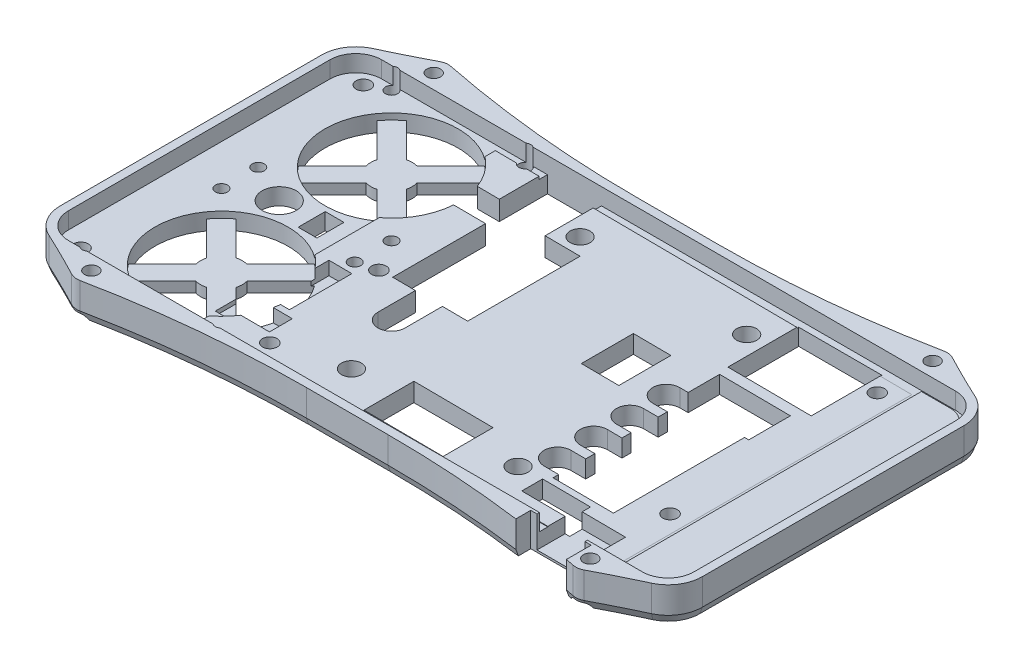
SolidWorks part; units mm, degrees
ref_plane "前视基准面" through (0, 0, 0) normal (0, 0, 1) x (1, 0, 0)
ref_plane "上视基准面" through (0, 0, 0) normal (0, 1, 0) x (1, 0, 0)
ref_plane "右视基准面" through (0, 0, 0) normal (1, 0, 0) x (0, 0, -1)
sketch "草图1" plane through (0, 0, 0) normal (0, 1, 0) x (1, 0, 0)
  line L0 (6, 0.2) -> (143.8, 0.2)
  line L1 (6, 0) -> (143.8, 0) construction
  line L2 (0, -6) -> (0, -68.8) construction
  line L3 (6, -74.8) -> (143.8, -74.8) construction
  line L4 (149.8, -6) -> (149.8, -68.8) construction
  line L5 (150, -6) -> (150, -68.8)
  line L6 (6, -75) -> (143.8, -75)
  line L7 (-0.2, -6) -> (-0.2, -68.8)
  arc A0 (143.8, 0) -> (149.8, -6) centre (143.8, -6) cw construction
  arc A1 (143.8, -74.8) -> (149.8, -68.8) centre (143.8, -68.8) ccw construction
  arc A2 (0, -68.8) -> (6, -74.8) centre (6, -68.8) ccw construction
  arc A3 (6, 0) -> (0, -6) centre (6, -6) ccw construction
  arc A4 (143.8, 0.2) -> (150, -6) centre (143.8, -6) cw
  arc A5 (143.8, -75) -> (150, -68.8) centre (143.8, -68.8) ccw
  arc A6 (-0.2, -68.8) -> (6, -75) centre (6, -68.8) ccw
  arc A7 (6, 0.2) -> (-0.2, -6) centre (6, -6) ccw
  point P7 (149.8, 0)
  point P12 (0, -74.8)
  point P15 (0, 0)
  dimension "D3" = 6
  dimension "D1" = 74.8
  dimension "D2" = 149.8
  dimension "D4" = 0.2
extrude "凸台-拉伸1" add sketch "草图1" along normal blind 4
sketch "草图2" plane through (0, 0, 0) normal (0, -1, 0) x (-1, 0, 0)
  line L0 (-122.6, -55.35) -> (-108.9, -55.35)
  line L1 (-122.6, -69.85) -> (-108.9, -69.85)
  line L2 (-122.6, -69.85) -> (-122.6, -63.95)
  line L3 (-122.6, -63.95) -> (-108.9, -63.95)
  line L4 (-108.9, -69.85) -> (-108.9, -63.95)
  line L5 (-135.3, -1.25) -> (-35.3, -1.25) construction
  line L6 (-135.3, -1.25) -> (-135.3, -73.55) construction
  line L7 (-135.3, -73.55) -> (-35.3, -73.55) construction
  line L8 (-35.3, -1.25) -> (-35.3, -73.55) construction
  line L9 (-108.9, -61.25) -> (-108.9, -55.35)
  line L10 (-122.6, -61.25) -> (-108.9, -61.25)
  line L11 (-122.6, -61.25) -> (-122.6, -55.35)
  line L12 (-122.6, -46.75) -> (-108.9, -46.75)
  line L13 (-108.9, -52.65) -> (-108.9, -46.75)
  line L14 (-122.6, -52.65) -> (-108.9, -52.65)
  line L15 (-122.6, -52.65) -> (-122.6, -46.75)
  line L16 (-122.6, -38.15) -> (-108.9, -38.15)
  line L17 (-108.9, -44.05) -> (-108.9, -38.15)
  line L18 (-122.6, -44.05) -> (-108.9, -44.05)
  line L19 (-122.6, -44.05) -> (-122.6, -38.15)
  line L20 (0, -6) -> (0, -68.8) construction
  line L21 (-35.3, -73.55) -> (-0.8, -73.55) construction
  line L22 (-120.25, -26.65) -> (-111.25, -26.65) construction
  line L23 (-120.25, -26.65) -> (-120.25, -33.15) construction
  line L24 (-120.25, -33.15) -> (-111.25, -33.15) construction
  line L25 (-111.25, -26.65) -> (-111.25, -33.15) construction
  line L26 (-85.8, -48.75) -> (-81.1, -48.75) construction
  line L27 (-85.8, -48.75) -> (-85.8, -58.15) construction
  line L28 (-85.8, -58.15) -> (-81.1, -58.15) construction
  line L29 (-81.1, -48.75) -> (-81.1, -58.15) construction
  line L30 (-71.5, -48.65) -> (-68.2, -48.65) construction
  line L31 (-71.5, -48.65) -> (-71.5, -57.55) construction
  line L32 (-71.5, -57.55) -> (-68.2, -57.55) construction
  line L33 (-68.2, -48.65) -> (-68.2, -57.55) construction
  line L34 (-43.1, -45.05) -> (-38.6, -45.05) construction
  line L35 (-43.1, -45.05) -> (-43.1, -59.05) construction
  line L36 (-43.1, -59.05) -> (-38.6, -59.05) construction
  line L37 (-38.6, -45.05) -> (-38.6, -59.05) construction
  line L38 (-45.3, -61.55) -> (-33.3, -61.55) construction
  line L39 (-45.3, -61.55) -> (-45.3, -66.05) construction
  line L40 (-45.3, -66.05) -> (-33.3, -66.05) construction
  line L41 (-33.3, -61.55) -> (-33.3, -66.05) construction
  line L42 (-0.8, -73.55) -> (-0.8, -1.25) construction
  line L43 (-0.8, -1.25) -> (-35.3, -1.25) construction
  line L44 (-149.8, -6) -> (-149.8, -68.8) construction
  line L45 (-30.8, -34.65) -> (-27.3, -34.65) construction
  line L46 (-30.8, -34.65) -> (-30.8, -40.15) construction
  line L47 (-30.8, -40.15) -> (-27.3, -40.15) construction
  line L48 (-27.3, -34.65) -> (-27.3, -40.15) construction
  line L49 (-120.75, -33.65) -> (-110.75, -33.65)
  line L50 (-110.75, -26.15) -> (-110.75, -33.65)
  line L51 (-120.75, -26.15) -> (-110.75, -26.15)
  line L52 (-120.75, -26.15) -> (-120.75, -33.65)
  line L53 (-86.3, -48.25) -> (-86.3, -58.65)
  line L54 (-86.3, -58.65) -> (-80.6, -58.65)
  line L55 (-80.6, -48.25) -> (-80.6, -58.65)
  line L56 (-86.3, -48.25) -> (-80.6, -48.25)
  line L57 (-72, -48.15) -> (-72, -58.05)
  line L58 (-72, -58.05) -> (-67.7, -58.05)
  line L59 (-67.7, -48.15) -> (-67.7, -58.05)
  line L60 (-72, -48.15) -> (-67.7, -48.15)
  line L61 (-31.3, -34.15) -> (-31.3, -40.65)
  line L62 (-31.3, -40.65) -> (-26.8, -40.65)
  line L63 (-26.8, -34.15) -> (-26.8, -40.65)
  line L64 (-31.3, -34.15) -> (-26.8, -34.15)
  line L65 (-43.6, -44.55) -> (-43.6, -59.55)
  line L66 (-43.6, -59.55) -> (-38.1, -59.55)
  line L67 (-38.1, -44.55) -> (-38.1, -59.55)
  line L68 (-43.6, -44.55) -> (-38.1, -44.55)
  line L69 (-45.8, -61.05) -> (-45.8, -66.55)
  line L70 (-45.8, -66.55) -> (-32.8, -66.55)
  line L71 (-32.8, -61.05) -> (-32.8, -66.55)
  line L72 (-45.8, -61.05) -> (-32.8, -61.05)
  circle A0 centre (-103.2, -9.35) radius 2 construction
  circle A1 centre (-103.2, -64.25) radius 2 construction
  circle A2 centre (-63.2, -64.25) radius 2 construction
  circle A3 centre (-63.2, -9.35) radius 2 construction
  circle A4 centre (-130.8, -5.6) radius 1.25 construction
  circle A5 centre (-131.1, -55.65) radius 1.25 construction
  circle A6 centre (-47.7, -4.85) radius 1.25 construction
  circle A7 centre (-48.1, -68.75) radius 1.25 construction
  circle A8 centre (-22.8, -70.3) radius 1.25 construction
  circle A9 centre (-5.05, -71.05) radius 1.25 construction
  circle A10 centre (-5.05, -3.25) radius 1.25 construction
  circle A11 centre (-19, -37.4) radius 3.6 construction
  circle A12 centre (-103.2, -9.35) radius 2.4
  circle A13 centre (-63.2, -9.35) radius 2.4
  circle A14 centre (-63.2, -64.25) radius 2.4
  circle A15 centre (-103.2, -64.25) radius 2.4
  circle A16 centre (-19, -37.4) radius 4.1
  circle A17 centre (-130.8, -5.6) radius 1.75
  circle A18 centre (-131.1, -55.65) radius 1.75
  circle A19 centre (-48.1, -68.75) radius 1.75
  circle A20 centre (-22.8, -70.3) radius 1.75
  circle A21 centre (-5.05, -71.05) radius 1.75
  circle A22 centre (-5.05, -3.25) radius 1.75
  circle A23 centre (-47.7, -4.85) radius 1.75
  circle A24 centre (-46.11, -40.57) radius 1.25 construction
  circle A25 centre (-46.11, -40.57) radius 1.75
  point P22 (0, -37.4)
  point P23 (-135.3, -37.4)
  point P28 (-115.75, -33.15)
  point P29 (-115.75, -38.15)
  point P30 (-111.25, -29.9)
  point P31 (-108.9, -41.1)
  point P79 (-0.8, -37.4)
  point P81 (-27.3, -37.4)
  dimension "D21" = 4
  dimension "D34" = 2.5
  dimension "D53" = 7.2
  dimension "D1" = 13.7
  dimension "D2" = 5.9
  dimension "D3" = 72.3
  dimension "D4" = 3.7
  dimension "D5" = 12.7
  dimension "D7" = 14.5
  dimension "D8" = 100
  dimension "D9" = 2.7
  dimension "D10" = 9
  dimension "D11" = 6.5
  dimension "D12" = 11.2
  dimension "D13" = 15.4
  dimension "D14" = 9.4
  dimension "D15" = 4.7
  dimension "D16" = 23.1
  dimension "D17" = 3.3
  dimension "D18" = 8.9
  dimension "D19" = 16
  dimension "D20" = 37.4
  dimension "D22" = 8.1
  dimension "D23" = 32.1
  dimension "D24" = 40
  dimension "D25" = 9.3
  dimension "D26" = 14
  dimension "D27" = 4.5
  dimension "D28" = 12
  dimension "D29" = 4.5
  dimension "D30" = 3.3
  dimension "D31" = 2
  dimension "D32" = 7.5
  dimension "D33" = 14.5
  dimension "D35" = 34.5
  dimension "D36" = 2
  dimension "D37" = 4.25
  dimension "D38" = 2.5
  dimension "D39" = 3.25
  dimension "D40" = 22
  dimension "D41" = 4.8
  dimension "D42" = 12.8
  dimension "D43" = 3.6
  dimension "D44" = 12.4
  dimension "D45" = 4.35
  dimension "D46" = 4.5
  dimension "D47" = 4.2
  dimension "D48" = 17.9
  dimension "D49" = 18.2
  dimension "D50" = 3.5
  dimension "D51" = 5.5
  dimension "D52" = 8.3
  dimension "D58" = 28.18
  dimension "D59" = 1.99
  dimension "D54" = 0.4
  dimension "D55" = 0.5
  dimension "D56" = 0.5
  dimension "D57" = 0.5
  dimension "D6" = 4
sketch "草图7" plane through (0, 0, -0.2) normal (0, 0, -1) x (-1, 0, 0)
  line L0 (-135.3, 4) -> (-35.3, 4.75)
  line L2 (-35.3, 4.75) -> (-35.3, 4)
  line L4 (-35.3, 4) -> (-135.3, 4)
  line L6 (-143.8, 4) -> (-6, 4) construction
  dimension "D1" = 0.75
extrude "凸台-拉伸11" add sketch "草图7" against normal offset from surface (71.2 mm away) 2 from offset 2 up to face at (74.9, 2, 75) offset against normal yes
extrude "切除-拉伸1" cut sketch "草图2" against normal blind 10 contours A12 | A13 | A14 | A15
sketch "草图3" plane through (0, 0, 0) normal (0, 1, 0) x (1, 0, 0)
  line L0 (136.8, -1) -> (136.8, -73.8)
  line L1 (143.8, 0) -> (135.8, 0) construction
  line L2 (149.8, -6) -> (149.8, -68.8) construction
  line L3 (143.8, -74.8) -> (135.8, -74.8) construction
  line L4 (135.8, 0) -> (135.8, -74.8) construction
  line L5 (6, -74.8) -> (143.8, -74.8) construction
  line L6 (135.3, -1.25) -> (135.3, -73.55) construction
  line L7 (143.8, -73.8) -> (136.8, -73.8)
  line L8 (148.8, -6) -> (148.8, -68.8)
  line L9 (143.8, -1) -> (136.8, -1)
  arc A0 (143.8, 0) -> (149.8, -6) centre (143.8, -6) cw construction
  arc A1 (149.8, -68.8) -> (143.8, -74.8) centre (143.8, -68.8) cw construction
  arc A2 (148.8, -68.8) -> (143.8, -73.8) centre (143.8, -68.8) cw
  arc A3 (143.8, -1) -> (148.8, -6) centre (143.8, -6) cw
  point P17 (149.8, 0)
  dimension "D1" = 6
  dimension "D2" = 0.5
extrude "凸台-拉伸9" add sketch "草图3" along normal offset from surface (5 mm away) 1 up to face at (85.3, 4, 37.4) offset beyond the face yes
sketch "草图4" plane through (0, 0, 0) normal (0, 1, 0) x (1, 0, 0)
  line L0 (125.2, -20.85) -> (108.2, -20.85)
  line L1 (108.2, -30.85) -> (109.7, -30.85)
  line L2 (109.7, -30.85) -> (109.7, -62.35)
  line L3 (108.7, -68.85) -> (108.7, -62.35)
  line L4 (49.2, -40.35) -> (49.2, -13.35)
  line L5 (108.2, -30.85) -> (108.2, -20.85)
  line L6 (108.7, -68.85) -> (120.2, -68.85)
  line L7 (108.2, -30.85) -> (125.2, -30.85) construction
  line L8 (109.7, -62.35) -> (124.2, -62.35)
  line L9 (80.466, -18.85) -> (96.6871, -18.85) construction
  line L10 (107.2, 11.628) -> (107.2, 24.7853) construction
  line L11 (49.2, -13.35) -> (67.2, -13.35)
  line L12 (125.2, -30.85) -> (124.2, -30.85)
  line L13 (124.2, -30.85) -> (124.2, -62.35)
  line L14 (124.2, -62.35) -> (120.2, -62.35)
  line L15 (120.2, -62.35) -> (120.2, -68.85)
  line L16 (67.2, -13.35) -> (67.2, -40.35)
  line L17 (67.2, -40.35) -> (49.2, -40.35)
  line L18 (63.2, -9.35) -> (46.0308, -9.35) construction
  line L19 (106.2, -55.55) -> (106.2, -28.85) construction
  line L20 (108.7, -63.85) -> (120.2, -63.85)
  line L21 (125.2, -20.85) -> (125.2, -30.85)
  line L22 (106.2, -28.4) -> (108.2, -28.4)
  line L23 (106.2, -34.9) -> (109.7, -34.9)
  line L24 (106.2, -37.1) -> (109.7, -37.1)
  line L25 (109.7, -37.1) -> (109.7, -43.6)
  line L26 (109.7, -43.6) -> (106.2, -43.6)
  line L27 (106.2, -45.8) -> (109.7, -45.8)
  line L28 (106.2, -52.3) -> (109.7, -52.3)
  line L29 (106.2, -54.5) -> (109.7, -54.5)
  line L30 (106.2, -61) -> (109.7, -61)
  line L31 (54.65, -49.35) -> (54.65, -40.35)
  line L32 (61.15, -49.35) -> (61.15, -40.35)
  line L33 (89.5, -35.35) -> (89.5, -22.85)
  line L34 (89.5, -22.85) -> (98.5, -22.85)
  line L35 (98.5, -22.85) -> (98.5, -35.35)
  line L36 (98.5, -35.35) -> (89.5, -35.35)
  line L37 (58.8, -1.85) -> (58.8, -13.85)
  line L38 (58.8, -13.85) -> (45.8, -13.85)
  line L39 (107.7, -18.35) -> (107.7, -1.35)
  line L40 (107.7, -1.35) -> (127.7, -1.35)
  line L41 (127.7, -1.35) -> (127.7, -18.35)
  line L42 (127.7, -18.35) -> (107.7, -18.35)
  line L43 (92.2, -59.25) -> (92.2, -71.25)
  line L44 (92.2, -71.25) -> (73.2, -71.25)
  line L45 (73.2, -71.25) -> (73.2, -59.25)
  line L46 (73.2, -59.25) -> (92.2, -59.25)
  line L47 (45.8, -13.85) -> (45.8, -1.85)
  line L48 (45.8, -1.85) -> (58.8, -1.85)
  line L49 (45.8, -11.35) -> (39.8, -11.35)
  line L50 (39.8, -11.35) -> (39.8, -18.05)
  line L51 (39.8, -18.05) -> (45.8, -18.05)
  line L52 (45.8, -18.05) -> (45.8, -11.35)
  line L53 (45.8, -18.05) -> (49.2, -18.05)
  line L54 (45.8, -1.85) -> (45.8, 0.2)
  line L55 (143.8, 0.2) -> (6, 0.2) construction
  line L56 (45.8, 0.2) -> (58.8, 0.2)
  line L57 (58.8, 0.2) -> (58.8, -1.85)
  circle A0 centre (103.2, -9.35) radius 2.4 construction
  circle A1 centre (103.2, -64.25) radius 2.4 construction
  circle A2 centre (103.2, -64.25) radius 2.4
  circle A3 centre (63.2, -64.25) radius 2.4 construction
  circle A4 centre (63.2, -64.25) radius 2.4
  circle A5 centre (103.2, -9.35) radius 2.4 construction
  circle A6 centre (106.2, -31.65) radius 3.25
  circle A7 centre (106.2, -40.35) radius 3.25
  circle A8 centre (106.2, -49.05) radius 3.25
  circle A9 centre (106.2, -57.75) radius 3.25
  circle A10 centre (63.2, -9.35) radius 2.4 construction
  circle A11 centre (63.2, -9.35) radius 2.4 construction
  circle A12 centre (57.9, -49.35) radius 3.25
  point P30 (67.2, -26.85)
  dimension "D7" = 9.5
  dimension "D30" = 4.5
  dimension "D40" = 6.5
  dimension "D18" = 6.5
  dimension "D21" = 4.5
  dimension "D4" = 11.5
  dimension "D5" = 48
  dimension "D6" = 10
  dimension "D8" = 4
  dimension "D9" = 5
  dimension "D10" = 5
  dimension "D11" = 17
  dimension "D12" = 6.5
  dimension "D13" = 1
  dimension "D14" = 14
  dimension "D15" = 18
  dimension "D16" = 4
  dimension "D17" = 27
  dimension "D19" = 40
  dimension "D20" = 5.3
  dimension "D22" = 4.4
  dimension "D23" = 13
  dimension "D24" = 1.5
  dimension "D25" = 12.5
  dimension "D26" = 5.5
  dimension "D27" = 9
  dimension "D28" = 8.7
  dimension "D29" = 12
  dimension "D31" = 20
  dimension "D32" = 9
  dimension "D33" = 17
  dimension "D34" = 11
  dimension "D35" = 19
  dimension "D36" = 12
  dimension "D37" = 7
  dimension "D38" = 11.5
  dimension "D39" = 22.3
  dimension "D41" = 3
  dimension "D43" = 13.5
  dimension "D44" = 4.7
  dimension "D45" = 6
  dimension "D46" = 2.5
  dimension "D47" = 6.7
  dimension "D42" = 4
extrude "拉伸-薄壁1" add sketch "草图1<2>" along normal blind 8 thin thin type one direction wall 2
sketch "草图1<2>" plane through (0, 0, 0) normal (0, 1, 0) x (1, 0, 0) same geometry as "草图1"
extrude "切除-拉伸2" cut sketch "草图4" along normal through all contours L20 L3 L6 L15 | A9 L30 L2 L29 | A8 L28 L2 L27 | A7 L26 L2 L24 | A6 L23 L2 L1 | A6 L5 L22 | A12 L17 L31 | A12 L32 L17 | L52 L53 L4 L38 | L57 L56 L54 L48 | L41 L42 L39 L40 | L8 L2 L1 L5 L0 L21 L12 L13 | A6 | A7 | A8 | A9 | L46 L43 L44 L45 | L35 L36 L33 L34 | L4 L11 L16 L17 | A12 | L47 L48 L37 L38 | L50 L51 L52 L49 region at (114.45, 0, 66.35) region at (107.7112, 0, 28.6021) region at (108.9903, 0, 33.7511) region at (109.6262, 0, 40.35) region at (107.95, 0, 60.9262) region at (109.6262, 0, 49.05) region at (47.5, 0, 15.95) region at (57.9, 0, 43.6145) region at (52.3, 0, 0.825)
extrude "切除-拉伸3" cut sketch "草图2<11>" against normal through all contours L61 L62 L63 L64 | A16
sketch "草图2<11>" plane through (0, 0, 0) normal (0, -1, 0) x (-1, 0, 0) same geometry as "草图2"
extrude "切除-拉伸4" cut sketch "草图2<13>" against normal through all contours A17 | A18 | A19 | A23 | A22 | A21 | A25
sketch "草图2<13>" plane through (0, 0, 0) normal (0, -1, 0) x (-1, 0, 0) same geometry as "草图2"
extrude "切除-拉伸5" cut sketch "草图2<14>" against normal through all from offset 1.5 contours L67 L66 L65 L68 | L71 L70 L69 L72 offset against normal yes
sketch "草图2<14>" plane through (0, 0, 0) normal (0, -1, 0) x (-1, 0, 0) same geometry as "草图2"
sketch "草图5" plane through (0, 0, 0) normal (0, -1, 0) x (-1, 0, 0)
  text T0 "<b>M3*6</b>" font "@Adobe 黑体 Std R" height 7
  text T1 "<b>M3*6</b>" font "@Adobe 黑体 Std R" height 7
  text T2 "<b>M3*6</b>" font "@Adobe 黑体 Std R" height 7
  text T3 "<b>M3*6</b>" font "@Adobe 黑体 Std R" height 7
extrude "切除-拉伸6" [suppressed] cut sketch "草图5" against normal blind 0.6
sketch "草图6" plane through (0, 0, 0) normal (0, 1, 0) x (1, 0, 0)
  line L1 (0, -6) -> (0, -68.8) construction
  line L2 (149.8, -6) -> (149.8, -68.8) construction
  line L4 (6, 0.2) -> (143.8, 0.2) construction
  line L5 (6, -75) -> (143.8, -75) construction
  circle A0 centre (15, 3.7) radius 1.5 construction
  circle A1 centre (15, -78.5) radius 1.5 construction
  circle A2 centre (134.8, 3.7) radius 1.5 construction
  circle A3 centre (134.8, -78.5) radius 1.5 construction
  circle A4 centre (15, 3.7) radius 3.5
  circle A5 centre (15, -78.5) radius 3.5
  circle A6 centre (134.8, 3.7) radius 3.5
  circle A7 centre (134.8, -78.5) radius 3.5
  circle A8 centre (15, 3.7) radius 1.65
  circle A9 centre (134.8, 3.7) radius 1.65
  circle A10 centre (134.8, -78.5) radius 1.65
  circle A11 centre (15, -78.5) radius 1.65
  dimension "D1" = 3
  dimension "D3" = 0.15
  dimension "D4" = 15
  dimension "D5" = 15
  dimension "D2" = 2
extrude "凸台-拉伸10" add sketch "草图6" along normal up to surface (8 mm away) up to face at (74.9, 8, 37.4)
extrude "切除-拉伸9" cut sketch "草图6<2>" along normal through all contours A8 | A9 | A10 | A11
sketch "草图6<2>" plane through (0, 0, 0) normal (0, 1, 0) x (1, 0, 0) same geometry as "草图6"
fillet "圆角1" radius 250 8 edges at (18.1623, 4, 77) (11.8377, 4, 77) (131.6377, 4, 77) (137.9623, 4, 77) (137.9623, 4, -2.2) (131.6377, 4, -2.2) (11.8377, 4, -2.2) (18.1623, 4, -2.2)
chamfer "倒角1" distance 0.6 angle 70 20 edges at (40.2731, 0, 78.2358) (14.5029, 0, 81.9645) (74.9, 0, 77) (7.988, 0, 78.8506) (109.5269, 0, 78.2358) (-0.9143, 0, 73.2083) (135.2971, 0, 81.9645) (-2.2, 0, 37.4) (141.812, 0, 78.8506) (-0.9143, 0, 1.5917) (150.7143, 0, 73.2083) (7.988, 0, -4.0506) (152, 0, 37.4) (14.5029, 0, -7.1645) (150.7143, 0, 1.5917) (40.2731, 0, -3.4358) (141.812, 0, -4.0506) (74.9, 0, -2.2) (135.2971, 0, -7.1645) (109.5269, 0, -3.4358) first distance on face at (134.8, 0, 80.15)
sketch "草图8" plane through (0, 0, 0) normal (0, -1, 0) x (1, 0, 0)
  line L0 (9.5525, 32.9807) -> (9.5525, 0.9807) construction
  line L1 (9.5525, 0.9807) -> (41.5525, 0.9807) construction
  line L2 (41.5525, 0.9807) -> (41.5525, 32.9807) construction
  line L3 (41.5525, 32.9807) -> (9.5525, 32.9807) construction
  line L4 (31.3, 37.4) -> (26.8, 37.4) construction
  line L7 (41.5525, 41.8193) -> (9.5525, 41.8193) construction
  line L8 (41.5525, 73.8193) -> (41.5525, 41.8193) construction
  line L9 (9.5525, 73.8193) -> (41.5525, 73.8193) construction
  line L10 (9.5525, 41.8193) -> (9.5525, 73.8193) construction
  circle A0 centre (41.5525, 0.9807) radius 1.45
  circle A1 centre (41.5525, 32.9807) radius 1.45
  circle A2 centre (9.5525, 32.9807) radius 1.45
  circle A3 centre (9.5525, 0.9807) radius 1.45
  circle A4 centre (9.5525, 73.8193) radius 1.45
  circle A5 centre (9.5525, 41.8193) radius 1.45
  circle A6 centre (41.5525, 41.8193) radius 1.45
  circle A7 centre (41.5525, 73.8193) radius 1.45
  point P4 (9.5525, 16.9807)
  dimension "D3" = 2.9
  dimension "D4" = 2.9
  dimension "D5" = 2.9
  dimension "D6" = 2.9
  dimension "D1" = 32
  dimension "D2" = 32
extrude "切除-拉伸10" cut sketch "草图8" against normal through all
sketch "草图9" plane through (0, 0, 0) normal (0, -1, 0) x (1, 0, 0)
  line L0 (9.5525, 32.9807) -> (41.5525, 32.9807) construction
  line L1 (41.5525, 32.9807) -> (41.5525, 0.9807) construction
  line L2 (41.5525, 0.9807) -> (9.5525, 0.9807) construction
  line L3 (9.5525, 0.9807) -> (9.5525, 32.9807) construction
  line L4 (9.5525, 32.9807) -> (41.5525, 0.9807) construction
  line L5 (41.5525, 32.9807) -> (9.5525, 0.9807) construction
  line L6 (13.088, 32.9807) -> (41.5525, 4.5163)
  line L7 (41.5525, 4.5163) -> (38.017, 0.9807)
  line L8 (38.017, 0.9807) -> (9.5525, 29.4452)
  line L9 (9.5525, 29.4452) -> (13.088, 32.9807)
  line L10 (38.017, 32.9807) -> (9.5525, 4.5163)
  line L11 (9.5525, 4.5163) -> (13.088, 0.9807)
  line L12 (13.088, 0.9807) -> (41.5525, 29.4452)
  line L13 (41.5525, 29.4452) -> (38.017, 32.9807)
  line L14 (9.5525, 0.9807) -> (41.5525, 0.9807) construction
  line L15 (31.3, 37.4) -> (26.8, 37.4) construction
  line L18 (9.5525, 73.8193) -> (41.5525, 73.8193) construction
  line L19 (9.5525, 41.8193) -> (41.5525, 73.8193) construction
  line L20 (9.5525, 73.8193) -> (9.5525, 41.8193) construction
  line L21 (41.5525, 73.8193) -> (9.5525, 73.8193) construction
  line L22 (41.5525, 41.8193) -> (41.5525, 73.8193) construction
  line L23 (9.5525, 41.8193) -> (41.5525, 41.8193) construction
  line L24 (41.5525, 45.3548) -> (38.017, 41.8193)
  line L25 (13.088, 73.8193) -> (41.5525, 45.3548)
  line L26 (9.5525, 70.2837) -> (13.088, 73.8193)
  line L27 (38.017, 41.8193) -> (9.5525, 70.2837)
  line L28 (9.5525, 45.3548) -> (13.088, 41.8193)
  line L29 (38.017, 73.8193) -> (9.5525, 45.3548)
  line L30 (41.5525, 70.2837) -> (38.017, 73.8193)
  line L31 (13.088, 41.8193) -> (41.5525, 70.2837)
  line L32 (41.5525, 41.8193) -> (9.5525, 73.8193) construction
  circle A0 centre (25.5525, 16.9807) radius 16
  circle A1 centre (25.5525, 16.9807) radius 5
  circle A2 centre (25.5525, 57.8193) radius 5
  circle A3 centre (25.5525, 57.8193) radius 16
  dimension "D2" = 10
  dimension "D4" = 5
extrude "切除-拉伸11" cut sketch "草图9" against normal blind 10 contours A1 L10 A0 L6 | A1 L6 A0 L12 | A1 L12 A0 L8 | A1 L8 A0 L10 | A3 L29 A2 L27 | A3 L25 A2 L29 | A3 L31 A2 L25 | A3 L27 A2 L31 region at (25.5525, 0, 28.2322) region at (14.301, 0, 16.9807) region at (36.804, 0, 16.9807) region at (25.5525, 0, 5.7292) region at (36.804, 0, 57.8193) region at (25.5525, 0, 46.5678) region at (14.301, 0, 57.8193) region at (25.5525, 0, 69.0708)
sketch "草图10" plane through (0, 4, 0) normal (0, 1, 0) x (1, 0, 0)
  circle A0 centre (25.5525, -16.9807) radius 16
  circle A1 centre (25.5525, -57.8193) radius 16
  dimension "D1" = 32
  dimension "D2" = 32
extrude "切除-拉伸12" cut sketch "草图10" against normal mid plane 3
sketch "草图11" plane through (0, 8, 0) normal (0, 1, 0) x (1, 0, 0)
  line L0 (119.1, -85.85) -> (119.1, -65.85)
  line L1 (119.1, -65.85) -> (130.6, -65.85)
  line L2 (130.6, -65.85) -> (130.6, -85.85)
  line L3 (130.6, -85.85) -> (119.1, -85.85)
  line L4 (120.2, -63.85) -> (108.7, -63.85) construction
  circle A0 centre (131.1, -55.65) radius 1.75 construction
  circle A1 centre (131.1, -55.65) radius 1.75 construction
  dimension "D1" = 11.5
  dimension "D2" = 0.5
  dimension "D3" = 2
  dimension "D4" = 20
extrude "切除-拉伸13" cut sketch "草图11" against normal blind 4.5 from surface starting at face at (143.4785, 5, 37.4)
sketch "草图12" plane through (0, 8, 0) normal (0, 1, 0) x (1, 0, 0)
  line L0 (117.6, -75.6) -> (117.6, -88.4406)
  line L1 (117.6, -88.4406) -> (132.1, -88.4406)
  line L2 (132.1, -88.4406) -> (132.1, -75.6)
  line L3 (132.1, -75.6) -> (117.6, -75.6)
  line L4 (42.3942, -75) -> (143.8, -75) construction
  line L5 (119.1, -73) -> (119.1, -75) construction
  line L6 (130.6, -75) -> (130.6, -73) construction
  dimension "D1" = 0.6
  dimension "D2" = 1.5
  dimension "D3" = 1.5
extrude "切除-拉伸14" cut sketch "草图12" against normal through all
sketch "草图13" plane through (0, 0, 75.6) normal (0, 0, 1) x (1, 0, 0)
  line L0 (130.6, 5) -> (130.6, 8)
  line L1 (132.1, 8) -> (117.6, 8) construction
  line L2 (130.6, 8) -> (119.1, 8)
  line L3 (119.1, 8) -> (119.1, 5)
  line L4 (119.1, 5) -> (130.6, 5)
extrude "切除-拉伸15" cut sketch "草图13" against normal up to next
sketch "草图14" plane through (0, 0, 0) normal (0, -1, 0) x (1, 0, 0)
  circle A0 centre (15, 78.5) radius 3.25
  circle A1 centre (15, -3.7) radius 3.25
  circle A2 centre (134.8, -3.7) radius 3.25
  circle A3 centre (134.8, 78.5) radius 3.25
  dimension "D1" = 6.5
extrude "切除-拉伸16" cut sketch "草图14" against normal blind 3
equation "\"D1@草图3\"=\"D3@草图1\""
